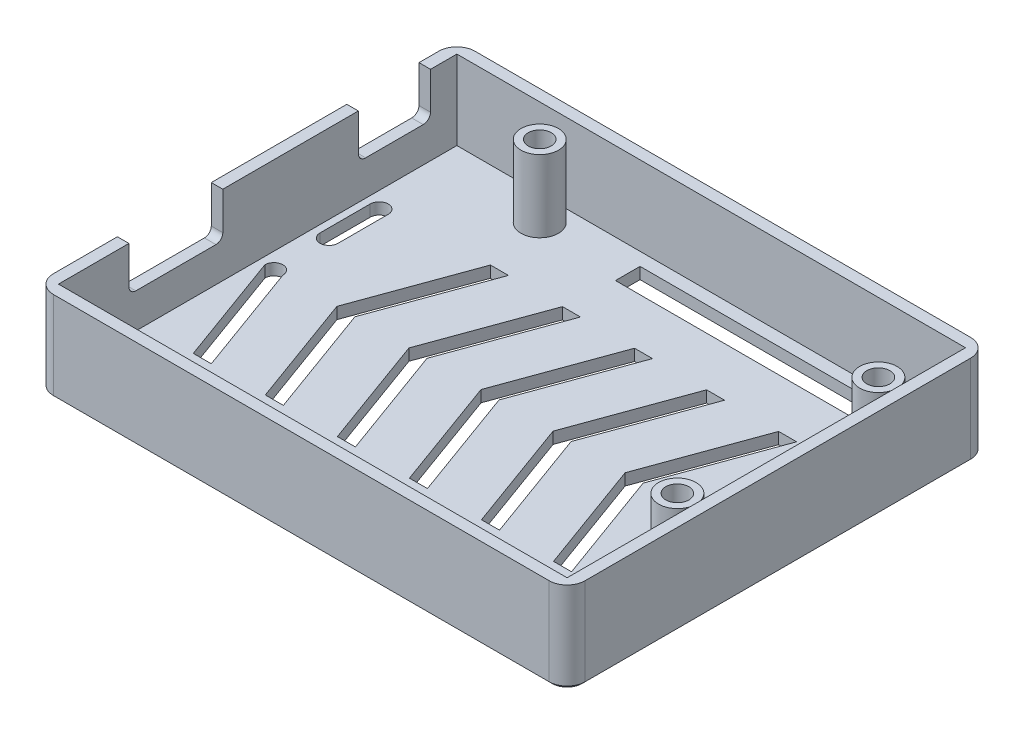
SolidWorks part; units mm, degrees
ref_plane "Front Plane" through (0, 0, 0) normal (0, 0, 1) x (1, 0, 0)
ref_plane "Top Plane" through (0, 0, 0) normal (0, 1, 0) x (1, 0, 0)
ref_plane "Right Plane" through (0, 0, 0) normal (1, 0, 0) x (0, 0, -1)
sketch "Sketch2" plane through (0, 0, 0) normal (0, 1, 0) x (1, 0, 0)
  line L0 (-1, 54.3) -> (69.6, 54.3)
  line L1 (0, 0) -> (68.6, 0) construction
  line L2 (0, 0) -> (0, 53.3) construction
  line L3 (0, 53.3) -> (68.6, 53.3) construction
  line L4 (68.6, 0) -> (68.6, 53.3) construction
  line L5 (69.6, -1) -> (69.6, 54.3)
  line L6 (-1, -1) -> (69.6, -1)
  line L7 (-1, -1) -> (-1, 54.3)
  circle A0 centre (14, 50.8) radius 1.6
  circle A1 centre (15.3, 2.6) radius 1.6
  circle A2 centre (66.1, 45.7) radius 1.6
  circle A3 centre (66.1, 17.8) radius 2.6
  circle A4 centre (14, 50.8) radius 2.6
  circle A5 centre (15.3, 2.6) radius 2.6
  circle A6 centre (66.1, 45.7) radius 2.6
  circle A7 centre (66.1, 17.8) radius 1.6
  dimension "D11" = 3.2
  dimension "D12" = 3.2
  dimension "D13" = 3.2
  dimension "D14" = 5.2
  dimension "D15" = 5.2
  dimension "D16" = 5.2
  dimension "D17" = 5.2
  dimension "D18" = 3.2
  dimension "D1" = 68.6
  dimension "D2" = 53.3
  dimension "D3" = 2.5
  dimension "D4" = 15.3
  dimension "D5" = 14
  dimension "D6" = 50.7
  dimension "D7" = 66.1
  dimension "D8" = 66.1
  dimension "D9" = 35.5
  dimension "D10" = 7.6
  dimension "D19" = 1
extrude "Boss-Extrude1" add sketch "Sketch2" along normal blind 11 contours L6 L5 L0 L7
shell "Shell1" thickness 1.6 removed face at (34.3, 11, -26.65) outward yes
fillet "Fillet1" radius 2.5 4 edges at (-2.6, 4.7, -55.9) (-2.6, 4.7, 2.6) (71.2, 4.7, -55.9) (71.2, 4.7, 2.6)
extrude "Boss-Extrude2" add sketch "Sketch2<4>" along normal blind 10 contours A2 | A4 | A0 | A6 | A7 | A3 region at (66.1, 0, -45.7)
sketch "Sketch2<4>" plane through (0, 0, 0) normal (0, 1, 0) x (1, 0, 0) same geometry as "Sketch2"
sketch "Sketch3" plane through (-2.6, 0, 0) normal (-1, 0, 0) x (0, 0, 1)
  line L0 (-9.28, 11) -> (-9.28, 5.78)
  line L1 (0.1, 11) -> (-53.4, 11) construction
  line L2 (0.1, -1.6) -> (0.1, 11) construction
  line L3 (-9.7373, 5.32) -> (-20.8533, 5.32)
  line L4 (-15.2953, 5.32) -> (-15.2953, 11) construction
  line L5 (-21.3106, 11) -> (-21.3106, 5.78)
  line L6 (-21.8106, 11) -> (-21.8106, 5.78)
  line L7 (-9.7358, 4.82) -> (-20.8548, 4.82)
  line L8 (-8.78, 11) -> (-8.78, 5.78)
  arc A0 (-9.28, 5.78) -> (-9.7373, 5.32) centre (-9.74, 5.78) cw
  arc A1 (-21.3106, 5.78) -> (-20.8533, 5.32) centre (-20.8506, 5.78) ccw
  arc A2 (-21.8106, 5.78) -> (-20.8548, 4.82) centre (-20.8506, 5.78) ccw
  arc A3 (-8.78, 5.78) -> (-9.7358, 4.82) centre (-9.74, 5.78) cw
  point P22 (0, 0)
  point P23 (0, 0)
  dimension "D2" = 0.46
  dimension "D3" = 11.116
  dimension "D1" = 9.38
  dimension "D4" = 5.22
  dimension "D5" = 0.5
sketch "Sketch4" plane through (-2.6, 0, 0) normal (-1, 0, 0) x (0, 0, 1)
  line L0 (-21.8106, 11) -> (-21.8106, 5.78)
  line L1 (-20.8548, 4.82) -> (-9.7358, 4.82)
  line L2 (-8.78, 5.78) -> (-8.78, 11)
  line L3 (-21.8106, 11) -> (-8.78, 11)
  arc A0 (-21.8106, 5.78) -> (-20.8548, 4.82) centre (-20.8506, 5.78) ccw
  arc A1 (-9.7358, 4.82) -> (-8.78, 5.78) centre (-9.7358, 5.7758) ccw
extrude "Cut-Extrude1" cut sketch "Sketch4" against normal blind 3
sketch "Sketch5" plane through (-2.6, 0, 0) normal (-1, 0, 0) x (0, 0, 1)
  line L0 (-50.14, 11) -> (-50.14, 5.85)
  line L1 (-21.8106, 11) -> (-53.4, 11) construction
  line L2 (-53.4, 11) -> (-53.4, -1.6) construction
  line L3 (-49.6312, 5.3589) -> (-41.6312, 5.3589)
  line L4 (-45.6312, 5.4298) -> (-45.6312, 11) construction
  line L5 (-41.1224, 11) -> (-41.1224, 5.85)
  line L6 (-50.64, 11) -> (-50.64, 5.8463)
  line L7 (-49.6276, 4.8589) -> (-41.6349, 4.8589)
  line L8 (-40.6224, 11) -> (-40.6224, 5.8463)
  arc A0 (-50.14, 5.85) -> (-49.6312, 5.3589) centre (-49.6401, 5.8589) ccw
  arc A1 (-41.1224, 5.85) -> (-41.6312, 5.3589) centre (-41.6224, 5.8589) cw
  arc A2 (-50.64, 5.8463) -> (-49.6276, 4.8589) centre (-49.6401, 5.8589) ccw
  arc A3 (-40.6224, 5.8463) -> (-41.6349, 4.8589) centre (-41.6224, 5.8589) cw
  dimension "D3" = 0.5
  dimension "D1" = 3.26
  dimension "D2" = 5.15
  dimension "D4" = 8
  dimension "D5" = 0.5
sketch "Sketch6" plane through (-2.6, 0, 0) normal (-1, 0, 0) x (0, 0, 1)
  line L0 (-50.64, 11) -> (-50.64, 5.8463)
  line L1 (-49.6276, 4.8589) -> (-41.6349, 4.8589)
  line L2 (-40.6224, 5.8463) -> (-40.6224, 11)
  line L3 (-40.6224, 11) -> (-50.64, 11)
  arc A0 (-50.64, 5.8463) -> (-49.6276, 4.8589) centre (-49.6401, 5.8589) ccw
  arc A1 (-41.6349, 4.8589) -> (-40.6224, 5.8463) centre (-41.6224, 5.8589) ccw
extrude "Cut-Extrude2" cut sketch "Sketch6" against normal blind 3
sketch "Sketch7" plane through (0, -1.6, 0) normal (0, -1, 0) x (-1, 0, 0)
  line L0 (-17.59, 1.32) -> (-64.83, 1.32)
  line L1 (0.1, -2.6) -> (-68.7, -2.6) construction
  line L2 (-64.83, 1.32) -> (-64.83, 3.73)
  line L3 (-71.2, -0.1) -> (-71.2, 53.4) construction
  line L4 (-64.83, 3.73) -> (-17.59, 3.73)
  line L5 (-17.59, 1.32) -> (-17.59, 3.73)
  line L6 (-64.83, -2.6) -> (-64.83, 49.58) construction
  line L7 (-64.83, 49.58) -> (-26.73, 49.58)
  line L8 (-64.83, 49.58) -> (-64.83, 51.99)
  line L9 (-64.83, 51.99) -> (-26.73, 51.99)
  line L10 (-26.73, 51.99) -> (-26.73, 49.58)
  line L11 (-17.09, 0.82) -> (-65.33, 0.82)
  line L12 (-65.33, 0.82) -> (-65.33, 4.23)
  line L13 (-65.33, 4.23) -> (-17.09, 4.23)
  line L14 (-17.09, 0.82) -> (-17.09, 4.23)
  line L15 (-65.33, 49.08) -> (-26.23, 49.08)
  line L16 (-26.23, 52.49) -> (-26.23, 49.08)
  line L17 (-65.33, 52.49) -> (-26.23, 52.49)
  line L18 (-65.33, 49.08) -> (-65.33, 52.49)
  dimension "D1" = 3.92
  dimension "D2" = 6.37
  dimension "D3" = 47.24
  dimension "D4" = 2.41
  dimension "D5" = 52.18
  dimension "D6" = 38.1
  dimension "D7" = 2.41
  dimension "D8" = 0.5
sketch "Sketch8" plane through (0, -1.6, 0) normal (0, -1, 0) x (1, 0, 0)
  line L0 (65.33, -0.82) -> (65.33, -4.23)
  line L1 (65.33, -4.23) -> (17.09, -4.23)
  line L2 (17.09, -4.23) -> (17.09, -0.82)
  line L3 (17.09, -0.82) -> (65.33, -0.82)
  line L4 (26.23, -49.08) -> (26.23, -52.49)
  line L5 (26.23, -52.49) -> (65.33, -52.49)
  line L6 (65.33, -52.49) -> (65.33, -49.08)
  line L7 (65.33, -49.08) -> (26.23, -49.08)
extrude "Cut-Extrude3" cut sketch "Sketch8" against normal blind 1.8
sketch "Sketch10" plane through (0, -1.6, 0) normal (0, -1, 0) x (-1, 0, 0)
  line L0 (0, 26.65) -> (-68.6, 26.65) construction
  line L1 (0, 0) -> (0, 53.3) construction
  line L2 (-68.6, 0) -> (-68.6, 53.3) construction
  line L3 (0, 26.65) -> (-5.6857, 11.0285)
  line L4 (-5.6857, 11.0285) -> (-8.1857, 11.0285)
  line L5 (-8.1857, 11.0285) -> (-2.5, 26.65)
  line L6 (-2.5, 26.65) -> (0, 26.65)
  line L7 (-18.1857, 11.0285) -> (-12.5, 26.65)
  line L8 (-15.6857, 11.0285) -> (-18.1857, 11.0285)
  line L9 (-28.1857, 11.0285) -> (-22.5, 26.65)
  line L10 (-25.6857, 11.0285) -> (-28.1857, 11.0285)
  line L11 (-38.1857, 11.0285) -> (-32.5, 26.65)
  line L12 (-35.6857, 11.0285) -> (-38.1857, 11.0285)
  line L13 (-48.1857, 11.0285) -> (-42.5, 26.65)
  line L14 (-45.6857, 11.0285) -> (-48.1857, 11.0285)
  line L15 (-58.1857, 11.0285) -> (-52.5, 26.65)
  line L16 (-55.6857, 11.0285) -> (-58.1857, 11.0285)
  line L17 (-15.6857, 11.0285) -> (-10, 26.65)
  line L19 (-25.6857, 11.0285) -> (-20, 26.65)
  line L21 (-35.6857, 11.0285) -> (-30, 26.65)
  line L23 (-45.6857, 11.0285) -> (-40, 26.65)
  line L25 (-55.6857, 11.0285) -> (-50, 26.65)
  line L27 (-45.6857, 42.2715) -> (-40, 26.65)
  line L28 (-45.6857, 42.2715) -> (-48.1857, 42.2715)
  line L29 (-48.1857, 42.2715) -> (-42.5, 26.65)
  line L30 (-35.6857, 42.2715) -> (-30, 26.65)
  line L31 (-35.6857, 42.2715) -> (-38.1857, 42.2715)
  line L32 (-38.1857, 42.2715) -> (-32.5, 26.65)
  line L33 (-25.6857, 42.2715) -> (-20, 26.65)
  line L34 (-25.6857, 42.2715) -> (-28.1857, 42.2715)
  line L35 (-28.1857, 42.2715) -> (-22.5, 26.65)
  line L36 (-15.6857, 42.2715) -> (-10, 26.65)
  line L37 (-15.6857, 42.2715) -> (-18.1857, 42.2715)
  line L38 (-18.1857, 42.2715) -> (-12.5, 26.65)
  line L39 (-55.6857, 42.2715) -> (-50, 26.65)
  line L40 (-55.6857, 42.2715) -> (-58.1857, 42.2715)
  line L41 (-58.1857, 42.2715) -> (-52.5, 26.65)
  line L46 (-2.5, 41.2721) -> (-2.5, 34.3098)
  line L48 (0, 34.3098) -> (0, 41.2721)
  arc A0 (0, 26.65) -> (-2.5, 26.65) centre (-1.25, 26.65) ccw
  arc A2 (-2.5, 41.2721) -> (0, 41.2721) centre (-1.25, 41.2721) cw
  arc A3 (-2.5, 34.3098) -> (0, 34.3098) centre (-1.25, 34.3098) ccw
  dimension "D1" = 70
  dimension "D2" = 2.5
  dimension "D3" = 6
extrude "Cut-Extrude4" cut sketch "Sketch10" against normal blind 3.5 contours L6 L5 L4 L3 | L6 A0 | L46 A3 L48 A2 | L17 L0 L7 L8 | L0 L36 L37 L38 | L19 L0 L9 L10 | L0 L33 L34 L35 | L21 L0 L11 L12 | L0 L30 L31 L32 | L23 L0 L13 L14 | L0 L27 L28 L29 | L25 L0 L15 L16 | L0 L39 L40 L41 region at (4.0929, -1.6, -18.8393) region at (54.0929, -1.6, -18.8393) region at (54.0929, -1.6, -34.4607) region at (44.0929, -1.6, -18.8393) region at (44.0929, -1.6, -34.4607) region at (34.0929, -1.6, -18.8393) region at (34.0929, -1.6, -34.4607) region at (24.0929, -1.6, -18.8393) region at (24.0929, -1.6, -34.4607) region at (14.0929, -1.6, -18.8393) region at (14.0929, -1.6, -34.4607) region at (1.25, -1.6, -27.1805) region at (1.25, -1.6, -37.7909)
chamfer "Chamfer1" distance 0.45 angle 45 8 edges at (70.4678, -1.6, 1.8678) (71.2, -1.6, -26.65) (70.4678, -1.6, -55.1678) (34.3, -1.6, -55.9) (-1.8678, -1.6, -55.1678) (34.3, -1.6, 2.6) (-1.8678, -1.6, 1.8678) (-2.6, -1.6, -26.65)
